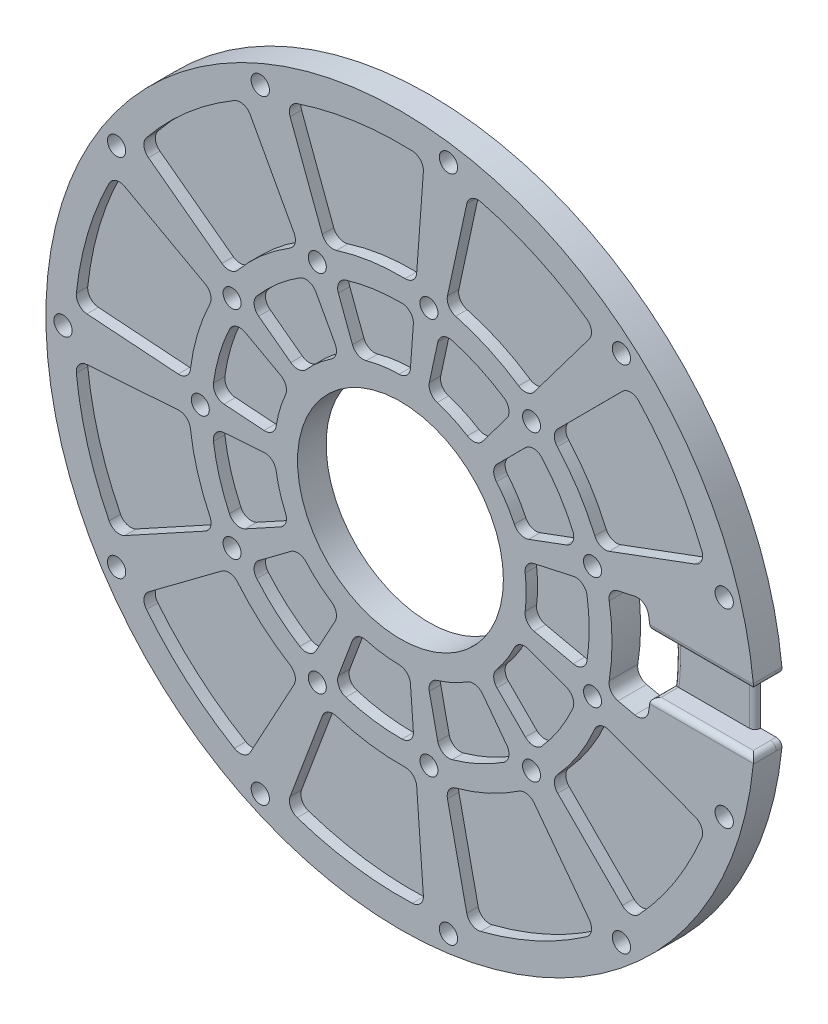
SolidWorks part; units mm, degrees
material "ABS"
ref_plane "Front Plane" through (0, 0, 0) normal (0, 0, 1) x (1, 0, 0)
ref_plane "Top Plane" through (0, 0, 0) normal (0, 1, 0) x (1, 0, 0)
ref_plane "Right Plane" through (0, 0, 0) normal (1, 0, 0) x (0, 0, -1)
sketch "Sketch1" plane through (0, 0, -63.9958) normal (0, 0, 1) x (1, 0, 0)
  circle A0 centre (89.0728, 47.2587) radius 62
  circle A2 centre (89.0728, 47.2587) radius 18
  dimension "D1" = 124
  dimension "D2" = 36
extrude "Boss-Extrude1" add sketch "Sketch1" along normal blind 5
sketch "Sketch2" plane through (0, 0, -58.9958) normal (0, 0, 1) x (1, 0, 0)
  line L0 (89.0728, 47.2587) -> (54.0728, 47.2587) construction
  circle A0 centre (54.0728, 47.2587) radius 1.575
  circle A1 centre (59.6289, 66.1811) radius 1.575
  circle A2 centre (74.5333, 79.0958) radius 1.575
  circle A3 centre (94.0538, 81.9025) radius 1.575
  circle A4 centre (111.9929, 73.7099) radius 1.575
  circle A5 centre (122.655, 57.1193) radius 1.575
  circle A6 centre (122.655, 37.3981) radius 1.575
  circle A7 centre (111.9929, 20.8075) radius 1.575
  circle A8 centre (94.0538, 12.615) radius 1.575
  circle A9 centre (74.5333, 15.4216) radius 1.575
  circle A10 centre (59.6289, 28.3363) radius 1.575
  point P27 (89.0728, 47.2587)
  dimension "D2" = 3.15
  dimension "D3" = 11
  dimension "D1" = 35
extrude "Cut-Extrude1" cut sketch "Sketch2" against normal through all
sketch "Sketch4" plane through (0, 0, -58.9958) normal (0, 0, 1) x (1, 0, 0)
  line L0 (89.0728, 47.2587) -> (30.0728, 47.2587) construction
  circle A0 centre (30.0728, 47.2587) radius 1.6
  circle A1 centre (39.4388, 79.1565) radius 1.6
  circle A2 centre (64.5633, 100.927) radius 1.6
  circle A3 centre (97.4694, 105.6582) radius 1.6
  circle A4 centre (127.7096, 91.8479) radius 1.6
  circle A5 centre (145.6829, 63.8809) radius 1.6
  circle A6 centre (145.6829, 30.6365) radius 1.6
  circle A7 centre (127.7096, 2.6695) radius 1.6
  circle A8 centre (97.4694, -11.1408) radius 1.6
  circle A9 centre (64.5633, -6.4096) radius 1.6
  circle A10 centre (39.4388, 15.3609) radius 1.6
  point P28 (89.0728, 47.2587)
  dimension "D2" = 3.2
  dimension "D1" = 59
  dimension "D3" = 11
extrude "Cut-Extrude3" cut sketch "Sketch4" against normal through all
sketch "Sketch3" plane through (0, 0, -58.9958) normal (0, 0, 1) x (1, 0, 0)
  line L0 (89.0728, 47.2587) -> (94.0538, 81.9025) construction
  line L1 (89.0728, 47.2587) -> (74.5333, 79.0958) construction
  line L2 (78.216, 76.2264) -> (80.6793, 69.654)
  line L3 (91.3287, 78.1118) -> (90.8168, 71.1116)
  line L44 (89.0728, 47.2587) -> (64.5633, 100.927) construction
  line L45 (89.0728, 47.2587) -> (97.4694, 105.6582) construction
  line L46 (75.4037, 83.73) -> (69.7833, 98.7263)
  line L47 (93.0808, 102.076) -> (91.913, 86.1037)
  line L52 (127.1182, 55.5982) -> (130.0522, 56.2414)
  line L53 (130.0522, 38.2761) -> (127.1182, 38.9192)
  line L68 (122.081, 91.207) -> (112.4633, 78.4017)
  line L69 (97.2915, 85.3304) -> (100.6709, 100.9847)
  line L70 (140.6014, 66.3848) -> (125.5873, 60.812)
  line L71 (116.5699, 74.8433) -> (127.8762, 86.1855)
  line L72 (142.7617, 35.4901) -> (127.1182, 38.9192) [skipped]
  line L73 (127.1182, 55.5982) -> (142.7617, 59.0273) [skipped]
  line L74 (127.8762, 8.3319) -> (116.5699, 19.6742)
  line L75 (125.5873, 33.7055) -> (140.6014, 28.1326)
  line L76 (100.6709, -6.4673) -> (97.2915, 9.187)
  line L77 (112.4633, 16.1158) -> (122.081, 3.3104)
  line L78 (69.7833, -4.2089) -> (75.4037, 10.7874)
  line L79 (91.913, 8.4137) -> (93.0808, -7.5586)
  line L80 (45.0199, 14.3901) -> (57.8558, 23.9671)
  line L81 (70.4609, 13.0447) -> (62.8081, -1.0234)
  line L82 (34.2431, 43.4246) -> (50.219, 44.5418)
  line L83 (54.918, 28.5384) -> (40.8742, 20.8409)
  line L84 (40.8742, 73.6765) -> (54.918, 65.979)
  line L85 (50.219, 49.9756) -> (34.2431, 51.0928)
  line L86 (62.8081, 95.5409) -> (70.4609, 81.4727)
  line L87 (57.8558, 70.5503) -> (45.0199, 80.1273)
  line L88 (95.6006, 77.4975) -> (94.1195, 70.6367)
  line L89 (107.651, 71.9943) -> (103.4358, 66.3821)
  line L90 (110.9127, 69.168) -> (105.9575, 64.1971)
  line L91 (118.0748, 58.0235) -> (111.4946, 55.5811)
  line L92 (119.2908, 53.8825) -> (112.4347, 52.3796)
  line L93 (119.2908, 40.635) -> (112.4347, 42.1378)
  line L94 (118.0748, 36.4939) -> (111.4946, 38.9363)
  line L95 (110.9127, 25.3494) -> (105.9575, 30.3204)
  line L96 (107.651, 22.5231) -> (103.4358, 28.1353)
  line L97 (95.6006, 17.0199) -> (94.1195, 23.8807)
  line L98 (91.3287, 16.4057) -> (90.8168, 23.4059)
  line L99 (78.216, 18.291) -> (80.6793, 24.8634)
  line L100 (74.2901, 20.0839) -> (77.6441, 26.2495)
  line L101 (64.2783, 28.7591) -> (69.9039, 32.9565)
  line L102 (61.945, 32.3899) -> (68.1, 35.7634)
  line L103 (58.2127, 45.1008) -> (65.2145, 45.5904)
  line L104 (58.2127, 49.4167) -> (65.2145, 48.927)
  line L105 (61.945, 62.1275) -> (68.1, 58.754)
  line L106 (64.2783, 65.7583) -> (69.9039, 61.5609)
  line L107 (74.2901, 74.4336) -> (77.6441, 68.2679)
  arc A0 (88.843, 69.2575) -> (83.0955, 68.4311) centre (89.0728, 47.2587) ccw
  arc A1 (89.3508, 80.2575) -> (79.5092, 78.8425) centre (89.0728, 47.2587) ccw
  arc A22 (91.3287, 78.1118) -> (89.3508, 80.2575) centre (89.334, 78.2576) ccw
  arc A23 (78.216, 76.2264) -> (79.5092, 78.8425) centre (80.0888, 76.9283) cw
  arc A24 (80.6793, 69.654) -> (83.0955, 68.4311) centre (82.5521, 70.3559) ccw
  arc A25 (90.8168, 71.1116) -> (88.843, 69.2575) centre (88.8222, 71.2574) cw
  arc A86 (77.8815, 82.5256) -> (89.875, 84.25) centre (89.0728, 47.2587) cw
  arc A87 (71.0227, 101.3253) -> (91.1594, 104.2205) centre (89.0728, 47.2587) cw
  arc A88 (91.913, 86.1037) -> (89.875, 84.25) centre (89.9183, 86.2495) cw
  arc A89 (93.0808, 102.076) -> (91.1594, 104.2205) centre (91.0862, 102.2218) ccw
  arc A90 (69.7833, 98.7263) -> (71.0227, 101.3253) centre (71.6561, 99.4282) cw
  arc A91 (75.4037, 83.73) -> (77.8815, 82.5256) centre (77.2765, 84.4319) ccw
  arc A104 (132.4522, 54.6225) -> (132.4522, 39.895) centre (89.0728, 47.2587) cw
  arc A106 (127.1182, 55.5982) -> (125.5734, 53.3171) centre (127.5464, 53.6446) ccw
  arc A107 (125.5734, 53.3171) -> (125.5734, 41.2003) centre (89.0728, 47.2587) cw
  arc A108 (127.1182, 38.9192) -> (125.5734, 41.2003) centre (127.5464, 40.8728) cw
  arc A152 (132.4522, 54.6225) -> (130.0522, 56.2414) centre (130.4804, 54.2877) ccw
  arc A153 (132.4522, 39.895) -> (130.0522, 38.2761) centre (130.4804, 40.2297) cw
  arc A154 (122.081, 91.207) -> (121.624, 94.0499) centre (120.4819, 92.4081) ccw
  arc A155 (103.1187, 102.501) -> (121.624, 94.0499) centre (89.0728, 47.2587) cw
  arc A156 (100.6709, 100.9847) -> (103.1187, 102.501) centre (102.6259, 100.5627) cw
  arc A157 (97.2915, 85.3304) -> (98.7248, 82.9776) centre (99.2465, 84.9084) ccw
  arc A158 (98.7248, 82.9776) -> (109.7466, 77.9441) centre (89.0728, 47.2587) cw
  arc A159 (112.4633, 78.4017) -> (109.7466, 77.9441) centre (110.8641, 79.6028) cw
  arc A160 (140.6014, 66.3848) -> (141.7539, 69.0235) centre (139.9054, 68.2598) ccw
  arc A161 (130.7552, 86.1377) -> (141.7539, 69.0235) centre (89.0728, 47.2587) cw
  arc A162 (127.8762, 86.1855) -> (130.7552, 86.1377) centre (129.2927, 84.7735) cw
  arc A163 (116.5699, 74.8433) -> (116.5036, 72.0891) centre (117.9864, 73.4313) ccw
  arc A164 (116.5036, 72.0891) -> (123.0545, 61.8958) centre (89.0728, 47.2587) cw
  arc A165 (125.5873, 60.812) -> (123.0545, 61.8958) centre (124.8913, 62.687) cw
  arc A166 (142.7617, 35.4901) -> (145.1578, 37.0869) centre (143.19, 37.4438) ccw [skipped]
  arc A167 (145.1578, 57.4306) -> (145.1578, 37.0869) centre (89.0728, 47.2587) cw [skipped]
  arc A168 (142.7617, 59.0273) -> (145.1578, 57.4306) centre (143.19, 57.0737) cw [skipped]
  arc A169 (127.1182, 55.5982) -> (125.5734, 53.3171) centre (127.5464, 53.6446) ccw [skipped]
  arc A170 (125.5734, 53.3171) -> (125.5734, 41.2003) centre (89.0728, 47.2587) cw [skipped]
  arc A171 (127.1182, 38.9192) -> (125.5734, 41.2003) centre (127.5464, 40.8728) cw [skipped]
  arc A172 (127.8762, 8.3319) -> (130.7552, 8.3797) centre (129.2927, 9.7439) ccw
  arc A173 (141.7539, 25.4939) -> (130.7552, 8.3797) centre (89.0728, 47.2587) cw
  arc A174 (140.6014, 28.1326) -> (141.7539, 25.4939) centre (139.9054, 26.2576) cw
  arc A175 (125.5873, 33.7055) -> (123.0545, 32.6216) centre (124.8913, 31.8305) ccw
  arc A176 (123.0545, 32.6216) -> (116.5036, 22.4283) centre (89.0728, 47.2587) cw
  arc A177 (116.5699, 19.6742) -> (116.5036, 22.4283) centre (117.9864, 21.0861) cw
  arc A178 (100.6709, -6.4673) -> (103.1187, -7.9836) centre (102.6259, -6.0453) ccw
  arc A179 (121.624, 0.4675) -> (103.1187, -7.9836) centre (89.0728, 47.2587) cw
  arc A180 (122.081, 3.3104) -> (121.624, 0.4675) centre (120.4819, 2.1093) cw
  arc A181 (112.4633, 16.1158) -> (109.7466, 16.5733) centre (110.8641, 14.9147) ccw
  arc A182 (109.7466, 16.5733) -> (98.7248, 11.5398) centre (89.0728, 47.2587) cw
  arc A183 (97.2915, 9.187) -> (98.7248, 11.5398) centre (99.2465, 9.6091) cw
  arc A184 (69.7833, -4.2089) -> (71.0227, -6.8079) centre (71.6561, -4.9108) ccw
  arc A185 (91.1594, -9.7031) -> (71.0227, -6.8079) centre (89.0728, 47.2587) cw
  arc A186 (93.0808, -7.5586) -> (91.1594, -9.7031) centre (91.0862, -7.7044) cw
  arc A187 (91.913, 8.4137) -> (89.875, 10.2674) centre (89.9183, 8.2679) ccw
  arc A188 (89.875, 10.2674) -> (77.8815, 11.9918) centre (89.0728, 47.2587) cw
  arc A189 (75.4037, 10.7874) -> (77.8815, 11.9918) centre (77.2765, 10.0855) cw
  arc A190 (45.0199, 14.3901) -> (44.6575, 11.5336) centre (46.216, 12.7871) ccw
  arc A191 (60.0323, -1.7887) -> (44.6575, 11.5336) centre (89.0728, 47.2587) cw
  arc A192 (62.8081, -1.0234) -> (60.0323, -1.7887) centre (61.0512, -0.0677) cw
  arc A193 (70.4609, 13.0447) -> (69.7486, 15.706) centre (68.7041, 14.0004) ccw
  arc A194 (69.7486, 15.706) -> (60.5913, 23.6408) centre (89.0728, 47.2587) cw
  arc A195 (57.8558, 23.9671) -> (60.5913, 23.6408) centre (59.0518, 22.3642) cw
  arc A196 (34.2431, 43.4246) -> (32.3938, 41.2175) centre (34.3826, 41.4295) ccw
  arc A197 (38.1253, 21.6979) -> (32.3938, 41.2175) centre (89.0728, 47.2587) cw
  arc A198 (40.8742, 20.8409) -> (38.1253, 21.6979) centre (39.9129, 22.5948) cw
  arc A199 (54.918, 28.5384) -> (55.7576, 31.1623) centre (53.9567, 30.2922) ccw
  arc A200 (55.7576, 31.1623) -> (52.3438, 42.7883) centre (89.0728, 47.2587) cw
  arc A201 (50.219, 44.5418) -> (52.3438, 42.7883) centre (50.3585, 42.5467) cw
  arc A202 (40.8742, 73.6765) -> (38.1253, 72.8195) centre (39.9129, 71.9226) ccw
  arc A203 (32.3938, 53.2999) -> (38.1253, 72.8195) centre (89.0728, 47.2587) cw
  arc A204 (34.2431, 51.0928) -> (32.3938, 53.2999) centre (34.3826, 53.0879) cw
  arc A205 (50.219, 49.9756) -> (52.3438, 51.7291) centre (50.3585, 51.9708) ccw
  arc A206 (52.3438, 51.7291) -> (55.7576, 63.3551) centre (89.0728, 47.2587) cw
  arc A207 (54.918, 65.979) -> (55.7576, 63.3551) centre (53.9567, 64.2252) cw
  arc A208 (62.8081, 95.5409) -> (60.0323, 96.3061) centre (61.0512, 94.5851) ccw
  arc A209 (44.6575, 82.9838) -> (60.0323, 96.3061) centre (89.0728, 47.2587) cw
  arc A210 (45.0199, 80.1273) -> (44.6575, 82.9838) centre (46.216, 81.7303) cw
  arc A211 (57.8558, 70.5503) -> (60.5913, 70.8766) centre (59.0518, 72.1533) ccw
  arc A212 (60.5913, 70.8766) -> (69.7486, 78.8115) centre (89.0728, 47.2587) cw
  arc A213 (70.4609, 81.4727) -> (69.7486, 78.8115) centre (68.7041, 80.517) cw
  arc A214 (107.1472, 74.8688) -> (98.1029, 78.9992) centre (89.0728, 47.2587) ccw
  arc A215 (95.6006, 77.4975) -> (98.1029, 78.9992) centre (97.5556, 77.0755) cw
  arc A216 (100.773, 65.8895) -> (95.491, 68.3017) centre (89.0728, 47.2587) ccw
  arc A217 (94.1195, 70.6367) -> (95.491, 68.3017) centre (96.0745, 70.2147) ccw
  arc A218 (103.4358, 66.3821) -> (100.773, 65.8895) centre (101.8366, 67.5832) cw
  arc A219 (107.651, 71.9943) -> (107.1472, 74.8688) centre (106.0518, 73.1954) ccw
  arc A220 (119.2051, 60.714) -> (113.8296, 69.0785) centre (89.0728, 47.2587) ccw
  arc A221 (110.9127, 69.168) -> (113.8296, 69.0785) centre (112.3292, 67.7561) cw
  arc A222 (108.9882, 56.6063) -> (105.8488, 61.4912) centre (89.0728, 47.2587) ccw
  arc A223 (105.9575, 64.1971) -> (105.8488, 61.4912) centre (107.3739, 62.7851) ccw
  arc A224 (111.4946, 55.5811) -> (108.9882, 56.6063) centre (110.7986, 57.4561) cw
  arc A225 (118.0748, 58.0235) -> (119.2051, 60.714) centre (117.3789, 59.8985) ccw
  arc A226 (121.6962, 42.2873) -> (121.6962, 52.2301) centre (89.0728, 47.2587) ccw
  arc A227 (119.2908, 53.8825) -> (121.6962, 52.2301) centre (119.719, 51.9288) cw
  arc A228 (110.8804, 44.3554) -> (110.8804, 50.162) centre (89.0728, 47.2587) ccw
  arc A229 (112.4347, 52.3796) -> (110.8804, 50.162) centre (112.8629, 50.426) ccw
  arc A230 (112.4347, 42.1378) -> (110.8804, 44.3554) centre (112.8629, 44.0914) cw
  arc A231 (119.2908, 40.635) -> (121.6962, 42.2873) centre (119.719, 42.5886) ccw
  arc A232 (113.8296, 25.4389) -> (119.2051, 33.8034) centre (89.0728, 47.2587) ccw
  arc A233 (118.0748, 36.4939) -> (119.2051, 33.8034) centre (117.3789, 34.6189) cw
  arc A234 (105.8488, 33.0262) -> (108.9882, 37.9111) centre (89.0728, 47.2587) ccw
  arc A235 (111.4946, 38.9363) -> (108.9882, 37.9111) centre (110.7986, 37.0613) ccw
  arc A236 (105.9575, 30.3204) -> (105.8488, 33.0262) centre (107.3739, 31.7323) cw
  arc A237 (110.9127, 25.3494) -> (113.8296, 25.4389) centre (112.3292, 26.7614) ccw
  arc A238 (98.1029, 15.5182) -> (107.1472, 19.6486) centre (89.0728, 47.2587) ccw
  arc A239 (107.651, 22.5231) -> (107.1472, 19.6486) centre (106.0518, 21.322) cw
  arc A240 (95.491, 26.2157) -> (100.773, 28.6279) centre (89.0728, 47.2587) ccw
  arc A241 (103.4358, 28.1353) -> (100.773, 28.6279) centre (101.8366, 26.9342) ccw
  arc A242 (94.1195, 23.8807) -> (95.491, 26.2157) centre (96.0745, 24.3027) cw
  arc A243 (95.6006, 17.0199) -> (98.1029, 15.5182) centre (97.5556, 17.4419) ccw
  arc A244 (79.5092, 15.6749) -> (89.3508, 14.2599) centre (89.0728, 47.2587) ccw
  arc A245 (91.3287, 16.4057) -> (89.3508, 14.2599) centre (89.334, 16.2598) cw
  arc A246 (83.0955, 26.0863) -> (88.843, 25.2599) centre (89.0728, 47.2587) ccw
  arc A247 (90.8168, 23.4059) -> (88.843, 25.2599) centre (88.8222, 23.26) ccw
  arc A248 (80.6793, 24.8634) -> (83.0955, 26.0863) centre (82.5521, 24.1615) cw
  arc A249 (78.216, 18.291) -> (79.5092, 15.6749) centre (80.0888, 17.5891) ccw
  arc A250 (63.9519, 25.8592) -> (71.4662, 19.348) centre (89.0728, 47.2587) ccw
  arc A251 (74.2901, 20.0839) -> (71.4662, 19.348) centre (72.5332, 21.0396) cw
  arc A252 (72.5977, 32.6789) -> (76.9861, 28.8764) centre (89.0728, 47.2587) ccw
  arc A253 (77.6441, 26.2495) -> (76.9861, 28.8764) centre (75.8873, 27.2052) ccw
  arc A254 (69.9039, 32.9565) -> (72.5977, 32.6789) centre (71.0999, 31.3535) cw
  arc A255 (64.2783, 28.7591) -> (63.9519, 25.8592) centre (65.4743, 27.1561) ccw
  arc A256 (56.3703, 42.8377) -> (59.1715, 33.2976) centre (89.0728, 47.2587) ccw
  arc A257 (61.945, 32.3899) -> (59.1715, 33.2976) centre (60.9837, 34.1437) cw
  arc A258 (67.3306, 43.9005) -> (68.9665, 38.3291) centre (89.0728, 47.2587) ccw
  arc A259 (68.1, 35.7634) -> (68.9665, 38.3291) centre (67.1387, 37.5173) ccw
  arc A260 (65.2145, 45.5904) -> (67.3306, 43.9005) centre (65.354, 43.5952) cw
  arc A261 (58.2127, 45.1008) -> (56.3703, 42.8377) centre (58.3522, 43.1056) ccw
  arc A262 (59.1715, 61.2198) -> (56.3703, 51.6797) centre (89.0728, 47.2587) ccw
  arc A263 (58.2127, 49.4167) -> (56.3703, 51.6797) centre (58.3522, 51.4118) cw
  arc A264 (68.9665, 56.1883) -> (67.3306, 50.6169) centre (89.0728, 47.2587) ccw
  arc A265 (65.2145, 48.927) -> (67.3306, 50.6169) centre (65.354, 50.9222) ccw
  arc A266 (68.1, 58.754) -> (68.9665, 56.1883) centre (67.1387, 57.0001) cw
  arc A267 (61.945, 62.1275) -> (59.1715, 61.2198) centre (60.9837, 60.3737) ccw
  arc A268 (71.4662, 75.1694) -> (63.9519, 68.6582) centre (89.0728, 47.2587) ccw
  arc A269 (64.2783, 65.7583) -> (63.9519, 68.6582) centre (65.4743, 67.3613) cw
  arc A270 (76.9861, 65.6411) -> (72.5977, 61.8385) centre (89.0728, 47.2587) ccw
  arc A271 (69.9039, 61.5609) -> (72.5977, 61.8385) centre (71.0999, 63.1639) ccw
  arc A272 (77.6441, 68.2679) -> (76.9861, 65.6411) centre (75.8873, 67.3122) cw
  arc A273 (74.2901, 74.4336) -> (71.4662, 75.1694) centre (72.5332, 73.4779) ccw
  point P52 (89.0728, 47.2587)
  point P142 (89.0728, 47.2587)
  point P291 (89.0728, 47.2587)
  point P293 (89.0728, 47.2587)
  dimension "D1" = 33
  dimension "D2" = 22
  dimension "D5" = 44
  dimension "D6" = 6.5725
  dimension "D7" = 57
  dimension "D8" = 37
  dimension "D11" = 2
  dimension "D12" = 2
  dimension "D13" = 11
  dimension "D14" = 3.0037
  dimension "D10" = 15.9723
  dimension "D4" = 7.0002
  dimension "D3" = 2
  dimension "D15" = 37
  dimension "D16" = 11
  dimension "D9" = 4
extrude "Cut-Extrude2" cut sketch "Sketch3" against normal blind 2
extrude "Cut-Extrude5" cut sketch "Sketch3<3>" against normal through all contours A153 A104 A152 L52 A106 A107 A108 L53 region at (129.3712, 47.2587, -58.9958)
sketch "Sketch3<3>" plane through (0, 0, -58.9958) normal (0, 0, 1) x (1, 0, 0) same geometry as "Sketch3"
sketch "Sketch7" plane through (0, 0, -58.9958) normal (0, 0, 1) x (1, 0, 0)
  line L0 (133.0728, 47.2587) -> (151.0728, 47.2587) construction
  line L1 (132.7878, 52.2587) -> (151.0728, 52.2587)
  line L2 (132.7878, 42.2587) -> (151.0728, 42.2587)
  line L3 (132.7878, 52.2587) -> (132.7878, 42.2587)
  line L4 (151.0728, 47.2587) -> (151.0728, 52.2587)
  line L5 (151.0728, 47.2587) -> (151.0728, 42.2587)
  arc A0 (132.4522, 39.895) -> (132.4522, 54.6225) centre (89.0728, 47.2587) ccw construction
  circle A1 centre (89.0728, 47.2587) radius 62 construction
  dimension "D1" = 5
  dimension "D2" = 5
extrude "Cut-Extrude6" cut sketch "Sketch7" against normal blind 4 contours L4 L1 L3 L2 L5
fillet "Fillet1" radius 1 7 edges at (132.7878, 42.2587, -60.9958) (150.8709, 42.2587, -60.9958) (132.7878, 52.2587, -60.9958) (150.8709, 52.2587, -60.9958) (133.0728, 47.2587, -62.9958) (141.8293, 52.2587, -58.9958) (141.8293, 42.2587, -58.9958)
sketch "Sketch8" plane through (0, 0, -62.9958) normal (0, 0, 1) x (1, 0, 0)
  line L0 (149.777, 52.2587) -> (133.671, 52.2587) construction
  line L1 (155.0728, 42.2587) -> (147.0728, 42.2587)
  line L2 (155.0728, 42.2587) -> (155.0728, 52.2587)
  line L3 (155.0728, 52.2587) -> (147.0728, 52.2587)
  line L4 (147.0728, 42.2587) -> (147.0728, 52.2587)
  line L5 (155.0728, 42.2587) -> (147.0728, 52.2587) construction
  line L6 (155.0728, 52.2587) -> (147.0728, 42.2587) construction
  arc A0 (150.7721, 41.1603) -> (150.7721, 53.3571) centre (89.0728, 47.2587) ccw construction
  point P0 (151.0728, 47.2587)
  dimension "D1" = 8
extrude "Cut-Extrude7" cut sketch "Sketch8" against normal through all
fillet "Fillet2" radius 1 2 edges at (150.8709, 42.2587, -63.4958) (150.8709, 52.2587, -63.4958)
fillet "Fillet3" radius 1 1 edges at (147.0728, 47.2587, -62.9958)
equation "\"HousingIn\"=113"
equation "\"HousingOut\"=124"
equation "\"FrontCutout\"=36"
equation "\"D1@Sketch1\"=\"HousingOut\""
equation "\"D2@Sketch1\"=\"FrontCutout\""
equation "\"D1@Sketch4\"=\"HousingOut\"/2 -3"
